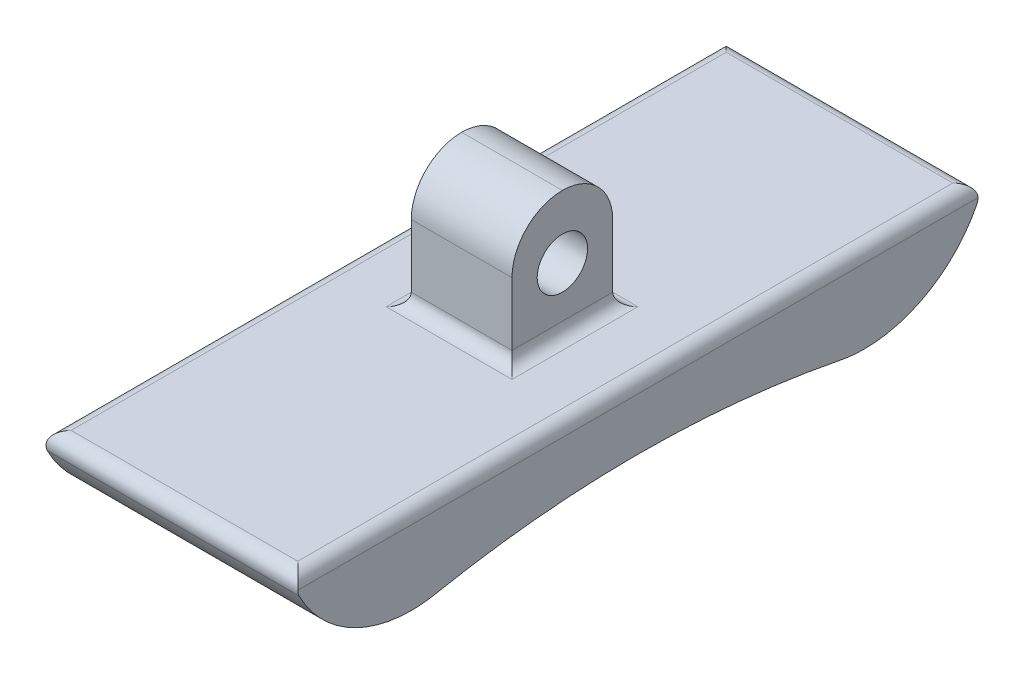
SolidWorks part; units mm, degrees
ref_plane "Alzado" through (0, 0, 0) normal (0, 0, 1) x (1, 0, 0)
ref_plane "Planta" through (0, 0, 0) normal (0, 1, 0) x (1, 0, 0)
ref_plane "Vista lateral" through (0, 0, 0) normal (1, 0, 0) x (0, 0, -1)
sketch "Croquis1" plane through (0, 0, 0) normal (1, 0, 0) x (0, 0, -1)
  line L1 (-28, 10) -> (28, 10)
  line L2 (-28, 10) -> (-28, 3.0962)
  line L4 (28, 10) -> (28, 3.0962)
  line L5 (-28, 10) -> (28, -10) construction
  line L6 (-28, -10) -> (28, 10) construction
  arc A0 (16.0697, -6.7157) -> (-16.0697, -6.7157) centre (0, -88.4) ccw
  arc A1 (16.0697, -6.7157) -> (28, 3.0962) centre (18, 3.0962) ccw
  arc A2 (-28, 3.0962) -> (-16.0697, -6.7157) centre (-18, 3.0962) ccw
  point P0 (0, 0)
  point P18 (0, 10)
  dimension "D1" = 10
  dimension "D2" = 10
  dimension "D3" = 56
extrude "Saliente-Extruir1" add sketch "Croquis1" along normal mid plane 20
sketch "Croquis2" plane through (0, 10, 0) normal (0, 1, 0) x (1, 0, 0)
  line L1 (4, -4) -> (-4, -4)
  line L2 (4, -4) -> (4, 4)
  line L3 (4, 4) -> (-4, 4)
  line L4 (-4, -4) -> (-4, 4)
  line L5 (4, -4) -> (-4, 4) construction
  line L6 (4, 4) -> (-4, -4) construction
  point P0 (0, 0)
  dimension "D1" = 8
  dimension "D2" = 8
extrude "Cortar-Extruir2" cut sketch "Croquis2" against normal blind 10 flip side to cut
sketch "Croquis3" plane through (-4, 0, 0) normal (-1, 0, 0) x (0, 0, 1)
  line L2 (4, 0) -> (4, 10) construction
  circle A0 centre (0, 5) radius 2
  point P5 (4, 5)
  dimension "D3" = 4
extrude "Cortar-Extruir3" cut sketch "Croquis3" against normal through all
sketch "Croquis6" plane through (0, 0, 0) normal (0, 0, 1) x (1, 0, 0)
  circle A0 centre (0, -55.8936) radius 50
  dimension "D1" = 100
extrude "Cortar-Extruir4" cut sketch "Croquis6" against normal through all both and the other way through all
fillet "Redondeo1" radius 1 8 edges at (-4, 0, 0) (0, 0, 4) (4, 0, 0) (0, 0, -4) (10, 0, 0) (-10, 0, 0) (0, 0, 27.5086) (0, 0, -27.5086)
fillet "Redondeo3" radius 4 2 edges at (0, 10, -4) (0, 10, 4)
